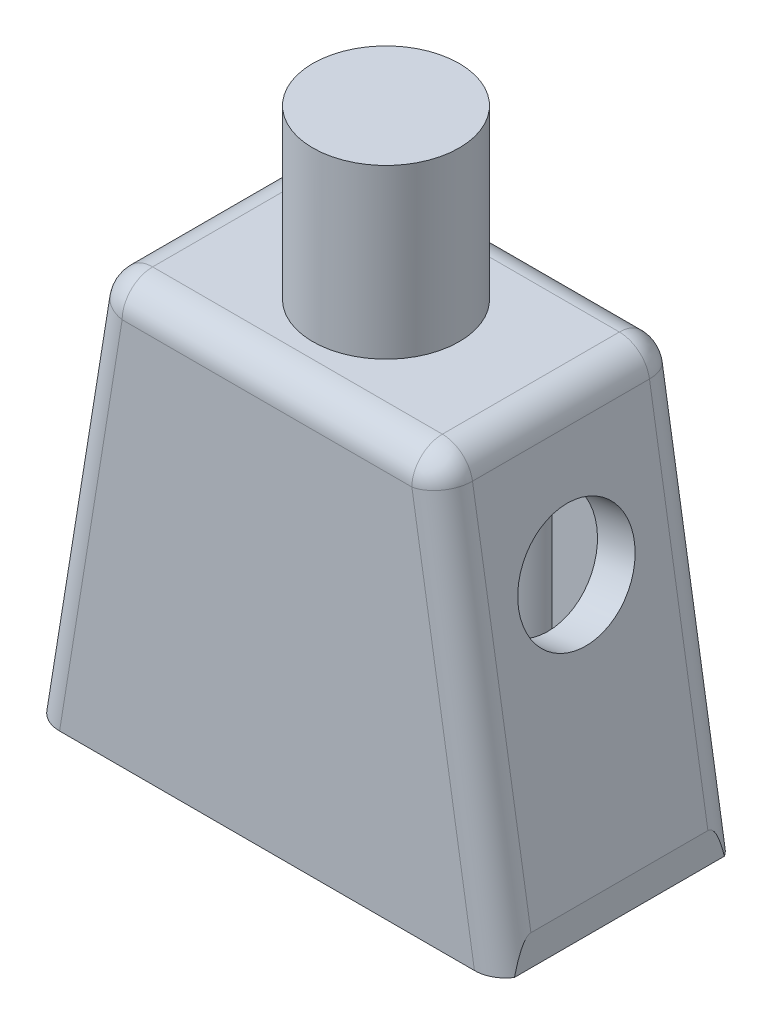
SolidWorks part; units mm, degrees
ref_plane "Front Plane" through (0, 0, 0) normal (0, 0, 1) x (1, 0, 0)
ref_plane "Top Plane" through (0, 0, 0) normal (0, 1, 0) x (1, 0, 0)
ref_plane "Right Plane" through (0, 0, 0) normal (1, 0, 0) x (0, 0, -1)
sketch "Sketch2" plane through (0, 0, 0) normal (0, 0, 1) x (1, 0, 0)
  line L0 (0, 25.9074) -> (0, -26.6172) construction
  line L1 (-7.65, 0) -> (7.65, 0)
  line L2 (7.65, 0) -> (7.65, 1)
  line L3 (7.65, 1) -> (5.5999, 13.7)
  line L4 (5.5999, 13.7) -> (2.3999, 13.7)
  line L8 (-5.5999, 13.7) -> (-2.3999, 13.7)
  line L9 (-7.65, 1) -> (-5.5999, 13.7)
  line L10 (-7.65, 0) -> (-7.65, 1)
  line L11 (-2.3999, 13.7) -> (2.3999, 13.7)
  point P12 (0, 0)
  dimension "D1" = 12.7
  dimension "D2" = 80.83
  dimension "D3" = 1
  dimension "D5" = 3.2
  dimension "D6" = 15.3
extrude "Boss-Extrude1" add sketch "Sketch2" along normal blind 7.8
fillet "Fillet1" radius 1 8 edges at (5.5999, 13.7, 3.9) (0, 13.7, 7.8) (-5.5999, 13.7, 3.9) (0, 13.7, 0) (6.6249, 7.35, 0) (6.6249, 7.35, 7.8) (-6.6249, 7.35, 7.8) (-6.6249, 7.35, 0)
sketch "Sketch3" plane through (0, 13.7, 0) normal (0, 1, 0) x (1, 0, 0)
  line L0 (0, 4.4573) -> (0, -10.6229) construction
  line L1 (-4.7484, -6.8) -> (4.7484, -6.8) construction
  line L2 (4.7484, -1) -> (-4.7484, -1) construction
  circle A0 centre (0, -3.9) radius 2.4
  point P2 (0, 0)
  point P8 (0, 0)
  point P9 (0, 0)
  point P10 (1.0492, -1.5426)
  point P15 (2.9114, 3.756)
  point P16 (0, 0)
  dimension "D1" = 4.8
  dimension "D2" = 2.9
  dimension "D3" = 2.9
extrude "Boss-Extrude2" add sketch "Sketch3" along normal blind 5.5
ref_plane "Plane1" through (0, 0, 4) normal (0, 0, 1) x (1, 0, 0)
shell "Shell3" thickness 1.25 removed face at (0, 0, 3.9)
sketch "Sketch7" plane through (7.613, 1.229, 0) normal (0.9872, 0.1594, 0) x (0, 0, -1)
  line L0 (-4, 8.415) -> (-4, -8.415) construction
  line L1 (-1, 11.781) -> (-6.8, 11.781) construction
  circle A0 centre (-4, 7.981) radius 1.9
  dimension "D1" = 3.8
  dimension "D2" = 3.8
extrude "Cut-Extrude5" cut sketch "Sketch7" against normal blind 2
mirror "Mirror1" about plane through (0, 0, 0) normal (1, 0, 0) of "Cut-Extrude5"
sketch "Sketch8" plane through (0, 0, 0) normal (0, -1, 0) x (1, 0, 0)
  line L0 (0, 4) -> (0, -1.027) construction
  line L1 (8.415, 4) -> (-8.415, 4) construction
  line L2 (0, 4) -> (0, 9.0509) construction
  line L3 (-7.65, 3.9) -> (-2.7904, 3.9) construction
  line L4 (1.5, 6.55) -> (1.5, 5.6929)
  line L5 (-6.4, 6.55) -> (6.4, 6.55) construction
  line L6 (4.5355, 6.55) -> (-4.5355, 6.55) construction
  line L7 (-1.5, 6.55) -> (-1.5, 5.6929)
  line L8 (-7.65, 7.3416) -> (-7.65, 0.4584) construction
  line L9 (1.5, 1.25) -> (1.5, 2.1071)
  line L10 (-1.5, 1.25) -> (-1.5, 2.1071)
  line L11 (2.7904, 6.55) -> (1.5, 6.55)
  line L12 (-1.5, 6.55) -> (-2.7904, 6.55)
  line L13 (2.7904, 1.25) -> (1.5, 1.25)
  line L14 (-1.5, 1.25) -> (-2.7904, 1.25)
  arc A0 (1.5, 5.6929) -> (2.7904, 6.55) centre (1.5, 7.0929) ccw
  arc A1 (-1.5, 5.6929) -> (-2.7904, 6.55) centre (-1.5, 7.0929) cw
  arc A2 (1.5, 2.1071) -> (2.7904, 1.25) centre (1.5, 0.7071) cw
  arc A3 (-1.5, 2.1071) -> (-2.7904, 1.25) centre (-1.5, 0.7071) ccw
  dimension "D2" = 1.4
  dimension "D3" = 1.2904
  dimension "D1" = 1.5
extrude "Boss-Extrude3" add sketch "Sketch8" against normal up to next
